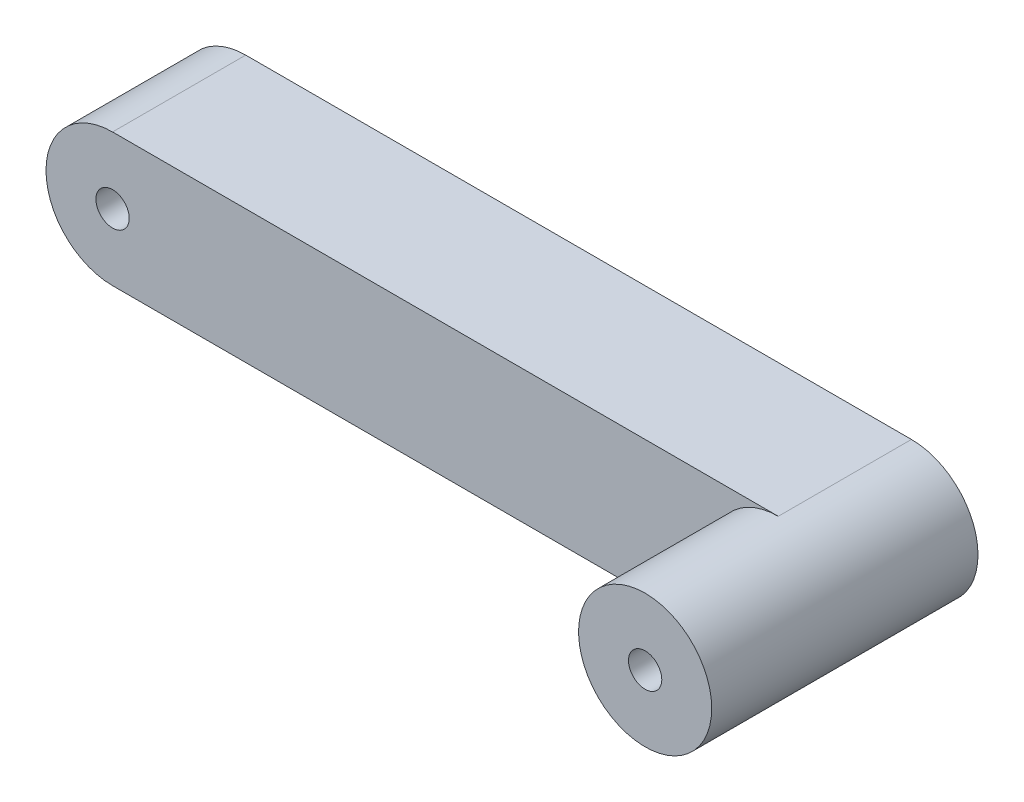
SolidWorks part; units mm, degrees
ref_plane "前视基准面" through (0, 0, 0) normal (0, 0, 1) x (1, 0, 0)
ref_plane "上视基准面" through (0, 0, 0) normal (0, 1, 0) x (1, 0, 0)
ref_plane "右视基准面" through (0, 0, 0) normal (1, 0, 0) x (0, 0, -1)
other "Configuration Table"
sketch "草图1" plane through (0, 0, 0) normal (0, 0, 1) x (1, 0, 0)
  line L0 (-1000, 0) -> (0, 0) construction
  line L2 (0, 2) -> (20, 2)
  line L3 (0, -2) -> (20, -2)
  line L4 (22, 0) -> (49000, 0) construction
  arc A0 (0, 2) -> (0, -2) centre (0, 0) ccw
  arc A1 (20, -2) -> (20, 2) centre (20, 0) ccw
  circle A2 centre (0, 0) radius 0.5
  circle A3 centre (20, 0) radius 0.5
  dimension "D1" = 4
  dimension "D3" = 4
  dimension "D4" = 1
  dimension "D5" = 1
  dimension "D2" = 20
extrude "凸台-拉伸1" add sketch "草图1" along normal blind 4
sketch "草图2" plane through (0, 0, 4) normal (0, 0, 1) x (1, 0, 0)
  circle A0 centre (20, 0) radius 2
  circle A1 centre (20, 0) radius 0.5
  dimension "D1" = 4
  dimension "D2" = 1
extrude "凸台-拉伸2" add sketch "草图2" along normal blind 4
